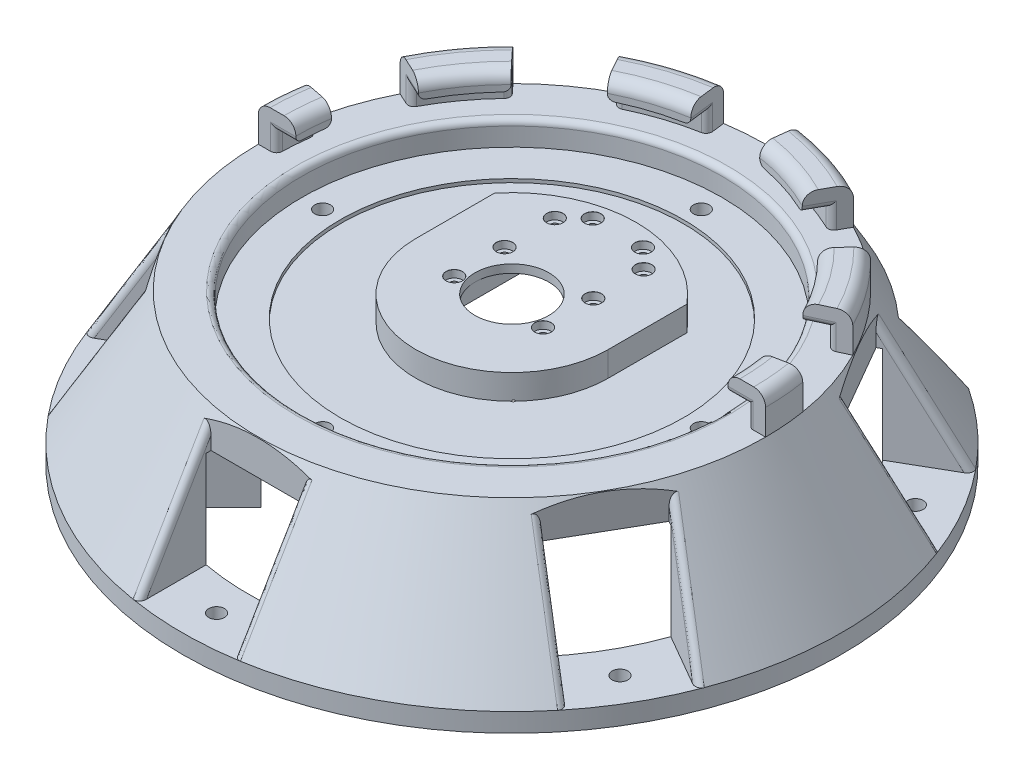
SolidWorks part; units mm, degrees
note: The reader was unsure of these and kept them because the rebuilt part matched: shared geometry of "Sketch3<3>".
material "PLA"
ref_plane "Front Plane" through (0, 0, 0) normal (0, 0, 1) x (1, 0, 0)
ref_plane "Top Plane" through (0, 0, 0) normal (0, 1, 0) x (1, 0, 0)
ref_plane "Right Plane" through (0, 0, 0) normal (1, 0, 0) x (0, 0, -1)
sketch "Sketch1" plane through (0, 0, 0) normal (0, 0, 1) x (1, 0, 0)
  line L0 (0, 0) -> (-85.725, 0)
  line L1 (-85.725, 0) -> (-115.0544, -50.8)
  line L2 (-115.0544, -50.8) -> (0, -50.8)
  line L6 (0, 0) -> (0, -50.8) construction
  line L7 (0, 0) -> (0, -50.8)
  dimension "D1" = 85.725
  dimension "D2" = 115.0544
  dimension "D3" = 50.8
revolve "Revolve1" add sketch "Sketch1" angle 360 about L6
sketch "Sketch2" plane through (0, 0, 0) normal (0, 1, 0) x (1, 0, 0)
  circle A0 centre (0, 0) radius 12.5
  dimension "D1" = 25
extrude "Cut-Extrude1" cut sketch "Sketch2" against normal through all
sketch "Sketch3" plane through (0, 0, 0) normal (0, 1, 0) x (1, 0, 0)
  line L0 (-32.5, 0) -> (-32.5, 26.6036)
  line L1 (-32.5, 26.6036) -> (32.5, 26.6036)
  line L2 (32.5, 26.6036) -> (32.5, 0)
  circle A0 centre (0, 0) radius 32.5
  circle A1 centre (0, 0) radius 71
  circle A2 centre (0, 0) radius 42
  circle M1 centre (0, 0) radius 12.5
  dimension "D1" = 65
  dimension "D2" = 142
  dimension "D3" = 84
extrude "Cut-Extrude2" cut sketch "Sketch3" against normal blind 8.2 contours A1 A0 L0 L1 L2 | A1 A2
sketch "Sketch7" plane through (0, -50.8, 0) normal (0, -1, 0) x (1, 0, 0)
  line L0 (0, 88.9) -> (0, -161.1) construction
  line L1 (-85.4, 0) -> (85.4, 0) construction
  line L2 (-60, -65.5989) -> (-60, -161.1)
  line L3 (-60, -161.1) -> (60, -161.1)
  line L4 (60, -161.1) -> (60, -65.5989)
  line L5 (-60, -65.5989) -> (60, -65.5989) construction
  arc A2 (60, -65.5989) -> (-60, -65.5989) centre (0, 0) ccw
  dimension "D1" = 177.8
  dimension "D2" = 25.4
  dimension "D3" = 25.4
  dimension "D4" = 120
  dimension "D5" = 250
extrude "Cut-Extrude5" cut sketch "Sketch7" against normal blind 39 contours L3 L4 A2 L2
sketch "Sketch8" plane through (0, 0, 0) normal (0, 1, 0) x (1, 0, 0)
  line L0 (0, 0) -> (0, -115.0544) construction
  line L2 (-15.875, -123.925) -> (15.875, -123.925)
  line L3 (-15.875, -123.925) -> (-15.875, -85.825)
  line L4 (-15.875, -85.825) -> (15.875, -85.825)
  line L5 (15.875, -123.925) -> (15.875, -85.825)
  line L6 (-15.875, -123.925) -> (15.875, -85.825) construction
  line L7 (-15.875, -85.825) -> (15.875, -123.925) construction
  arc A0 (-60, 98.1708) -> (60, 98.1708) centre (0, 0) ccw construction
  point P6 (0, -104.875)
  dimension "D1" = 85.825
  dimension "D2" = 38.1
  dimension "D3" = 31.75
extrude "Cut-Extrude6" cut sketch "Sketch8" against normal blind 44.45
pattern_circular "CirPattern2" count 6 over 360 about axis through (0, 0, 0) along (0, 1, 0) of "Cut-Extrude6"
sketch "Sketch9" plane through (0, 0, 0) normal (0, 1, 0) x (1, 0, 0)
  line L0 (0, 0) -> (0, -115.0544) construction
  arc A0 (-60, 98.1708) -> (60, 98.1708) centre (0, 0) ccw construction
  circle A1 centre (0, -99.8144) radius 2.65
  dimension "D1" = 5.3
  dimension "D2" = 15.24
extrude "Cut-Extrude7" cut sketch "Sketch9" against normal through all
pattern_circular "CirPattern3" count 6 over 360 about axis through (0, 0, 0) along (0, 1, 0) of "Cut-Extrude7"
sketch "Sketch12" plane through (0, 0, 0) normal (0, 0, 1) x (1, 0, 0)
  line L0 (85.725, 0) -> (85.725, 12.7)
  line L1 (85.725, 12.7) -> (73.025, 12.7)
  line L2 (73.025, 12.7) -> (73.025, 6.55)
  line L3 (73.025, 6.55) -> (79.575, 6.55)
  line L4 (79.575, 6.55) -> (79.575, 0)
  line L5 (85.725, 0) -> (-85.725, 0) construction
  line L6 (0, 0) -> (0, 12.7) construction
  line L7 (12.5, 0) -> (-12.5, 0) construction
  line L8 (79.575, 0) -> (85.725, 0)
  point P13 (0, 6.35)
  dimension "D1" = 6.15
  dimension "D2" = 73.025
  dimension "D3" = 79.575
  dimension "D4" = 12.7
  dimension "D5" = 12.7
revolve "Revolve2" add sketch "Sketch12" angle 180 about L6
sketch "Sketch15" plane through (0, -11.8, 0) normal (0, -1, 0) x (1, 0, 0)
  line L0 (0, -1000) -> (0, 49000) construction
  point P1 (-15, 4.5)
  point P4 (-15, -12.5)
  point P5 (-15, -29.5)
  point P6 (-8.5, -35.8)
  point P7 (8.5, -35.8)
  point P8 (15, -29.5)
  point P9 (15, -12.5)
  point P10 (15, 4.5)
  dimension "D1" = 17
  dimension "D2" = 17
  dimension "D3" = 4.5
  dimension "D4" = 15
  dimension "D5" = 8.5
  dimension "D6" = 35.8
sketch "Sketch18" plane through (0, 12.7, 0) normal (0, 1, 0) x (1, 0, 0)
  line L0 (46.6433, 89.7185) -> (70.9138, 72.0849)
  line L1 (0, 201000) -> (0, -249000) construction
  line L2 (-15, 100) -> (-9, 50)
  line L3 (-9, 50) -> (9, 50)
  line L4 (9, 50) -> (15, 100)
  line L5 (-15, 100) -> (15, 100)
  line L6 (36.6704, 35.1608) -> (70.9138, 72.0849)
  line L7 (22.1081, 45.7409) -> (36.6704, 35.1608)
  line L8 (46.6433, 89.7185) -> (22.1081, 45.7409)
  line L9 (90.4704, 45.1675) -> (99.7409, 16.6359)
  line L10 (50.334, 6.8913) -> (99.7409, 16.6359)
  line L11 (44.7717, 24.0104) -> (50.334, 6.8913)
  line L12 (90.4704, 45.1675) -> (44.7717, 24.0104)
  line L13 (99.7409, -16.6359) -> (90.4704, -45.1675)
  line L14 (44.7717, -24.0104) -> (90.4704, -45.1675)
  line L15 (50.334, -6.8913) -> (44.7717, -24.0104)
  line L16 (99.7409, -16.6359) -> (50.334, -6.8913)
  line L17 (70.9138, -72.0849) -> (46.6433, -89.7185)
  line L18 (22.1081, -45.7409) -> (46.6433, -89.7185)
  line L19 (36.6704, -35.1608) -> (22.1081, -45.7409)
  line L20 (70.9138, -72.0849) -> (36.6704, -35.1608)
  line L21 (15, -100) -> (-15, -100)
  line L22 (-9, -50) -> (-15, -100)
  line L23 (9, -50) -> (-9, -50)
  line L24 (15, -100) -> (9, -50)
  line L25 (-46.6433, -89.7185) -> (-70.9138, -72.0849)
  line L26 (-36.6704, -35.1608) -> (-70.9138, -72.0849)
  line L27 (-22.1081, -45.7409) -> (-36.6704, -35.1608)
  line L28 (-46.6433, -89.7185) -> (-22.1081, -45.7409)
  line L29 (-90.4704, -45.1675) -> (-99.7409, -16.6359)
  line L30 (-50.334, -6.8913) -> (-99.7409, -16.6359)
  line L31 (-44.7717, -24.0104) -> (-50.334, -6.8913)
  line L32 (-90.4704, -45.1675) -> (-44.7717, -24.0104)
  line L33 (-99.7409, 16.6359) -> (-90.4704, 45.1675)
  line L34 (-44.7717, 24.0104) -> (-90.4704, 45.1675)
  line L35 (-50.334, 6.8913) -> (-44.7717, 24.0104)
  line L36 (-99.7409, 16.6359) -> (-50.334, 6.8913)
  line L37 (-70.9138, 72.0849) -> (-46.6433, 89.7185)
  line L38 (-22.1081, 45.7409) -> (-46.6433, 89.7185)
  line L39 (-36.6704, 35.1608) -> (-22.1081, 45.7409)
  line L40 (-70.9138, 72.0849) -> (-36.6704, 35.1608)
  point P4 (0, 50)
  point P7 (0, 100)
  point P48 (0, 0)
  dimension "D1" = 18
  dimension "D2" = 50
  dimension "D3" = 30
  dimension "D4" = 50
  dimension "D5" = 10
extrude "Cut-Extrude9" cut sketch "Sketch18" against normal blind 12.7
sketch "Sketch20" plane through (0, -11.8, 0) normal (0, -1, 0) x (1, 0, 0)
  line L0 (-22.5, -33) -> (-12.5, -40)
  line L1 (23.5, 23) -> (-22.5, 23)
  line L2 (23.5, 23) -> (23.5, -40)
  line L3 (23.5, -40) -> (-22.5, -40)
  line L4 (-22.5, 23) -> (-22.5, -40)
  line L7 (-12.5, -40) -> (13.5, -40)
  line L8 (13.5, -40) -> (23.5, -33)
  point P0 (0, -10)
  dimension "D1" = 23
  dimension "D2" = 46
  dimension "D3" = 10
  dimension "D4" = 10
  dimension "D5" = 7
  dimension "D6" = 7
  dimension "D7" = 10
  dimension "D8" = 40
  dimension "D9" = 22.5
extrude "Cut-Extrude11" cut sketch "Sketch3<3>" against normal blind 1 contours A0 L1 M1 | A0 L1 L0 | L1 A0 | L1 A2 A0 | A0 L2 L1
sketch "Sketch3<3>" plane through (0, 0, 0) normal (0, 1, 0) x (1, 0, 0) same geometry as "Sketch3"
sketch "Sketch22" plane through (0, -1, 0) normal (0, 1, 0) x (1, 0, 0)
  circle A0 centre (-15, 12.5) radius 1.4
  circle A1 centre (-15, 29.5) radius 1.4
  circle A2 centre (-8.5, 35.8) radius 1.4
  circle A3 centre (8.5, 35.8) radius 1.4
  circle A4 centre (15, 29.5) radius 1.4
  circle A5 centre (15, 12.5) radius 1.4
  circle A6 centre (15, -4.5) radius 1.4
  circle A7 centre (-15, -4.5) radius 1.4
  dimension "D1" = 17
  dimension "D2" = 17
  dimension "D3" = 2.8
  dimension "D4" = 2.8
  dimension "D5" = 2.8
  dimension "D6" = 2.8
  dimension "D7" = 2.8
  dimension "D8" = 2.8
  dimension "D9" = 2.8
  dimension "D10" = 2.8
  dimension "D11" = 17
  dimension "D12" = 30
  dimension "D13" = 30
  dimension "D14" = 30
  dimension "D15" = 17
  dimension "D16" = 17
  dimension "D17" = 6.3
  dimension "D18" = 6.3
  dimension "D19" = 35.8
  dimension "D20" = 8.5
  dimension "D21" = 35.8
  dimension "D22" = 15
  dimension "D23" = 19.5256
  dimension "D24" = 15.6605
hole_wizard "CBORE for M2.5 SHCS1" positions "Sketch23" profile "Sketch24" counterbore size "M2.5" standard "ANSI Metric" end condition through all
sketch "Sketch23" plane through (0, -1, 0) normal (0, 1, 0) x (1, 0, 0)
  point P0 (-15, -4.5)
  point P3 (-15, 12.5)
  point P6 (-15, 29.5)
  point P9 (-8.5, 35.8)
  point P12 (8.5, 35.8)
  point P15 (15, 29.5)
  point P18 (15, 12.5)
  point P21 (15, -4.5)
sketch "Sketch24" plane through (-15, -1, 4.5) normal (1, 0, 0) x (0, 0, 1)
  line L0 (0, 0) -> (0, 49.8)
  line L1 (0, 49.8) -> (1.45, 49.8)
  line L3 (1.45, 49.8) -> (1.45, 2.5)
  line L4 (2.75, 2.5) -> (1.45, 2.5)
  line L5 (2.75, 2.5) -> (2.75, 0.025)
  line L6 (2.75, 0.025) -> (2.775, 0)
  line L7 (2.775, 0) -> (0, 0)
  line L8 (-2.75, 0.025) -> (-2.775, 0) construction
  line L11 (0, -6.35) -> (0, 107.95) construction
  dimension "Thru Hole Dia." = 2.9
  dimension "Thru Hole Depth" = 49.8
  dimension "C'Bore Dia." = 5.5
  dimension "C'Bore Depth" = 2.5
  dimension "Near C'Sink Dia." = 5.55
  dimension "Near C'Sink Angle" = 90
fillet "Fillet1" radius 4 12 edges at (85.4509, 12.7, -6.8497) (69.353, 12.7, -50.3879) (26.4905, 12.7, -81.5293) (-26.4905, 12.7, -81.5293) (-69.353, 12.7, -50.3879) (-85.4509, 12.7, -6.8497) (-72.8088, 12.7, -5.6148) (-59.0785, 12.7, -42.923) (-22.566, 12.7, -69.4509) (22.566, 12.7, -69.4509) (59.0785, 12.7, -42.923) (72.8088, 12.7, -5.6148)
fillet "Fillet2" radius 2 12 edges at (75.3771, 6.55, -11.8306) (76.3, 6.55, 0) (54.0275, 6.55, -53.8767) (67.9352, 6.55, -34.7344) (12.0413, 6.55, -75.3438) (34.5444, 6.55, -68.0321) (-12.0413, 6.55, -75.3438) (-34.5444, 6.55, -68.0321) (-54.0275, 6.55, -53.8767) (-67.9352, 6.55, -34.7344) (-75.3771, 6.55, -11.8306) (-76.3, 6.55, 0)
fillet "Fillet3" radius 2 12 edges at (-78.5927, 4.275, -12.4648) (-56.2562, 4.275, -56.2798) (-70.9094, 4.275, -36.1114) (-12.4317, 4.275, -78.5979) (56.2562, 4.275, -56.2798) (78.5927, 4.275, -12.4648) (-79.575, 4.275, 0) (-36.1412, 4.275, -70.8942) (12.4317, 4.275, -78.5979) (36.1412, 4.275, -70.8942) (70.9094, 4.275, -36.1114) (79.575, 4.275, 0)
fillet "Fillet4" radius 2 10 edges
fillet "Fillet5" radius 2 1 edges at (0, 0, 71)
fillet "Fillet9" radius 1 2 edges
sketch "Sketch28" plane through (0, -11.8, 0) normal (0, -1, 0) x (1, 0, 0)
  line L0 (9.2, 12) -> (-9.2, 12)
  line L1 (-12.2, 9) -> (-12.2, -30)
  line L2 (-9.2, -33) -> (9.2, -33)
  line L3 (12.2, -30) -> (12.2, 9)
  line L4 (9.2, 12.5) -> (-9.2, 12.5)
  line L5 (-12.7, 9) -> (-12.7, -30)
  line L6 (-9.2, -33.5) -> (9.2, -33.5)
  line L7 (12.7, -30) -> (12.7, 9)
  arc A0 (-9.2, 12) -> (-12.2, 9) centre (-9.2, 9) ccw
  arc A1 (-12.2, -30) -> (-9.2, -33) centre (-9.2, -30) ccw
  arc A2 (9.2, -33) -> (12.2, -30) centre (9.2, -30) ccw
  arc A3 (12.2, 9) -> (9.2, 12) centre (9.2, 9) ccw
  arc A4 (-9.2, 12.5) -> (-12.7, 9) centre (-9.2, 9) ccw
  arc A5 (-12.7, -30) -> (-9.2, -33.5) centre (-9.2, -30) ccw
  arc A6 (9.2, -33.5) -> (12.7, -30) centre (9.2, -30) ccw
  arc A7 (12.7, 9) -> (9.2, 12.5) centre (9.2, 9) ccw
  dimension "D1" = 0.5
extrude "Cut-Extrude12" cut sketch "Sketch28" against normal offset from surface (8.05 mm away) 2.75 contours L4 A4 L5 A5 L6 A6 L7 A7
extrude "Cut-Extrude15" cut sketch "Sketch20" against normal offset from surface (2.75 mm away) 2.75
sketch "Sketch29" plane through (0, -8.2, 0) normal (0, 1, 0) x (1, 0, 0)
  point P0 (0, 64)
  point P5 (64, 0)
  point P6 (0, -64)
  point P7 (-64, 0)
  point P8 (0, 0)
  dimension "D1" = 64
  dimension "D2" = 4
hole_wizard "M5 Clearance Hole1" positions "Sketch32" profile "Sketch33" hole size "M5" standard "ANSI Metric" end condition up to next
sketch "Sketch32" plane through (0, -8.2, 0) normal (0, 1, 0) x (1, 0, 0)
  point P0 (0, 64)
  point P3 (64, 0)
  point P6 (0, -64)
  point P9 (-64, 0)
sketch "Sketch33" plane through (0, -8.2, -64) normal (1, 0, 0) x (0, 0, 1)
  line L0 (0, 0) -> (0, 3.6)
  line L1 (0, 3.6) -> (2.65, 3.6)
  line L2 (2.65, 3.6) -> (2.65, 0)
  line L5 (2.65, 0) -> (0, 0)
  line L11 (0, -6.35) -> (0, 107.95) construction
  dimension "Thru Hole Dia." = 5.3
  dimension "Thru Hole Depth" = 3.6
sketch "Sketch34" plane through (0, -8.2, 0) normal (0, 1, 0) x (1, 0, 0)
  circle A0 centre (0, 0) radius 70
  circle A1 centre (0, 0) radius 58
  line M5 (-32.5, 0) -> (-32.5, 26.6036)
  arc M6 (-32.5, 26.6036) -> (32.5, 26.6036) centre (0, 0) cw
  line M7 (32.5, 26.6036) -> (32.5, 0)
  arc M8 (32.5, 0) -> (-32.5, 0) centre (0, 0) cw
  dimension "D1" = 140
  dimension "D2" = 116
extrude "Cut-Extrude16" cut sketch "Sketch34" against normal blind 1.2 contours A1 M8 M5 M6 M7
sketch "Sketch37" plane through (0, 0, 0) normal (0, 1, 0) x (1, 0, 0)
  circle A0 centre (0, 0) radius 111.3882
  dimension "D1" = 222.7764
sketch "Sketch39" plane through (0, -50.8, 0) normal (0, -1, 0) x (1, 0, 0)
  line L0 (-67.1751, 67.1751) -> (-42.4264, 42.4264)
  line L1 (-72, 12.5) -> (-107, 12.5)
  line L2 (-72, 12.5) -> (-72, -12.5)
  line L3 (-72, -12.5) -> (-107, -12.5)
  line L4 (-107, 12.5) -> (-107, -12.5)
  line L5 (-72, 0) -> (0, 0) construction
  line L6 (0, 0) -> (72, 0) construction
  line L7 (107, 12.5) -> (72, 12.5)
  line L8 (107, 12.5) -> (107, -12.5)
  line L9 (107, -12.5) -> (72, -12.5)
  line L10 (72, 12.5) -> (72, -12.5)
  line L13 (-42.4264, 42.4264) -> (-29.6985, 55.1543)
  line L14 (-29.6985, 55.1543) -> (-54.4472, 79.9031)
  line L15 (-54.4472, 79.9031) -> (-67.1751, 67.1751)
  line L16 (54.4472, 79.9031) -> (29.6985, 55.1543)
  line L17 (29.6985, 55.1543) -> (42.4264, 42.4264)
  line L18 (42.4264, 42.4264) -> (67.1751, 67.1751)
  line L19 (67.1751, 67.1751) -> (54.4472, 79.9031)
  line L21 (0, 0) -> (101.0152, 101.0152) construction
  line L22 (0, 0) -> (-104.6054, 104.6054) construction
  arc M26 (-60, -65.5989) -> (60, -65.5989) centre (0, 0) cw
  dimension "D1" = 25
  dimension "D2" = 35
  dimension "D3" = 35
  dimension "D4" = 35
  dimension "D5" = 72
  dimension "D6" = 72
  dimension "D7" = 60
  dimension "D8" = 60
  dimension "D9" = 18
  dimension "D10" = 18
  dimension "D11" = 35
  dimension "D12" = 25
extrude "Boss-Extrude1" add sketch "Sketch39" along a picked direction on the side against the normal up to next (39 mm away) contours L13 L14 L0 M26 | L3 L2 L1 M26 | L17 L18 L16 M26 | L7 L10 L9 M26
fillet "Fillet10" radius 10 2 edges at (36.0624, -11.8, 48.7904) (-36.0624, -11.8, 48.7904)
extrude "Cut-Extrude-Thin1" cut sketch "Sketch37" against normal through all thin
